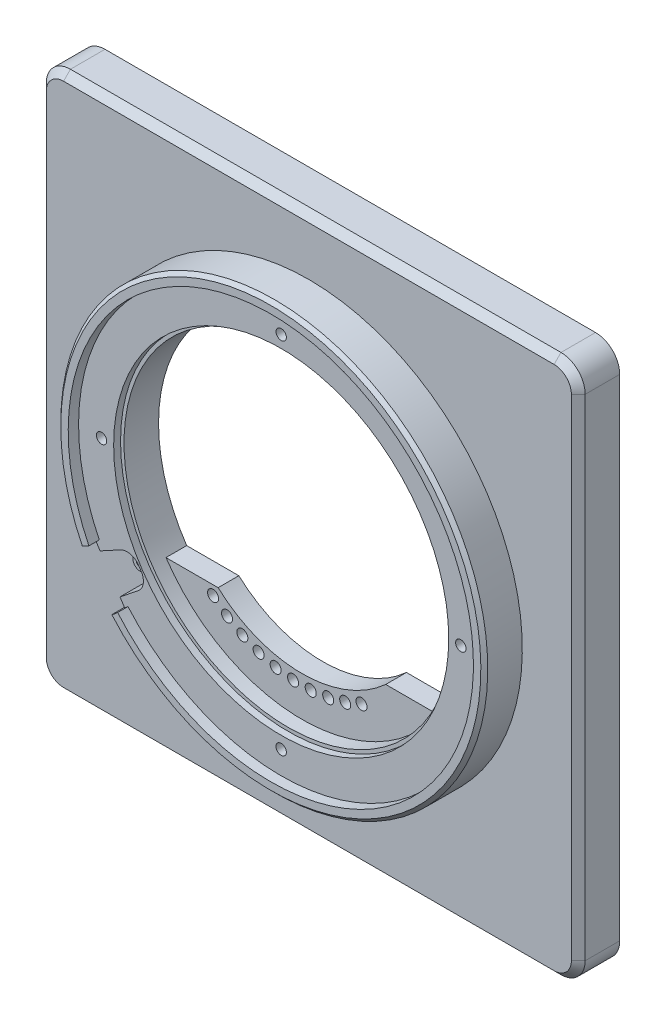
SolidWorks part; units mm, degrees
ref_plane "前视基准面" through (0, 0, 0) normal (0, 0, 1) x (1, 0, 0)
ref_plane "上视基准面" through (0, 0, 0) normal (0, 1, 0) x (1, 0, 0)
ref_plane "右视基准面" through (0, 0, 0) normal (1, 0, 0) x (0, 0, -1)
other "Configuration Table"
sketch "草图1" plane through (0, 0, 0) normal (0, 0, 1) x (1, 0, 0)
  line L1 (-39, -39) -> (39, -39)
  line L2 (-39, -39) -> (-39, 39)
  line L3 (-39, 39) -> (39, 39)
  line L4 (39, -39) -> (39, 39)
  line L5 (-39, -39) -> (39, 39) construction
  line L6 (-39, 39) -> (39, -39) construction
  circle A0 centre (0, 0) radius 23.75
  point P0 (0, 0)
  dimension "D2" = 47.5
  dimension "D1" = 78
extrude "凸台-拉伸1" add sketch "草图1" against normal blind 2
sketch "草图2" plane through (0, 0, 0) normal (0, 0, 1) x (1, 0, 0)
  circle A0 centre (0, 0) radius 23.75
  circle A1 centre (0, 0) radius 23.75 construction
  circle A2 centre (0, 0) radius 30.9
  dimension "D1" = 61.8
extrude "凸台-拉伸2" add sketch "草图2" along normal blind 4
sketch "草图3" plane through (0, 0, -2) normal (0, 0, -1) x (-1, 0, 0)
  line L1 (-39, -39) -> (39, -39)
  line L2 (-39, -39) -> (-39, 39)
  line L3 (-39, 39) -> (39, 39)
  line L4 (39, -39) -> (39, 39)
  line L5 (-39, -39) -> (39, 39) construction
  line L6 (-39, 39) -> (39, -39) construction
  line L7 (-37, -37) -> (37, -37)
  line L8 (-37, -37) -> (-37, 37)
  line L9 (-37, 37) -> (37, 37)
  line L10 (37, -37) -> (37, 37)
  line L11 (-37, -37) -> (37, 37) construction
  line L12 (-37, 37) -> (37, -37) construction
  line L13 (-37, 37) -> (-32, 37)
  line L14 (-37, 37) -> (-37, 32)
  line L15 (-37, 32) -> (-32, 32)
  line L16 (-32, 37) -> (-32, 32)
  line L17 (37, 37) -> (32, 37)
  line L18 (37, 37) -> (37, 32)
  line L19 (37, 32) -> (32, 32)
  line L20 (32, 37) -> (32, 32)
  line L21 (-37, -37) -> (-32, -37)
  line L22 (-37, -37) -> (-37, -32)
  line L23 (-37, -32) -> (-32, -32)
  line L24 (-32, -37) -> (-32, -32)
  line L25 (37, -37) -> (32, -37)
  line L26 (37, -37) -> (37, -32)
  line L27 (37, -32) -> (32, -32)
  line L28 (32, -37) -> (32, -32)
  point P0 (0, 0)
  point P7 (0, 0)
  line M23 (-39, 39) -> (-39, -39)
  line M24 (-39, -39) -> (39, -39)
  line M25 (39, -39) -> (39, 39)
  line M26 (39, 39) -> (-39, 39)
  dimension "D1" = 2
  dimension "D2" = 5
extrude "凸台-拉伸3" add sketch "草图3" along normal blind 4 contours L10 L7 L8 L9 M26 M23 M24 M25 | L16 L9 L8 L15 | L9 L20 L19 L10 | L28 L7 L10 L27 | L7 L24 L23 L8 region at (37.8969, 0, -2) region at (34.5, -34.5, -2) region at (-34.5, -34.5, -2) region at (34.5, 34.5, -2) region at (-34.5, 34.5, -2)
sketch "草图4" plane through (0, 0, 4) normal (0, 0, 1) x (1, 0, 0)
  line L0 (0, 26) -> (0, -26) construction
  line L1 (-26, 0) -> (26, 0) construction
  circle A0 centre (0, 0) radius 26 construction
  circle A1 centre (0, 26) radius 0.75
  circle A2 centre (26, 0) radius 0.75
  circle A3 centre (0, -26) radius 0.75
  circle A4 centre (-26, 0) radius 0.75
  dimension "D2" = 52
  dimension "D3" = 1.5
extrude "切除-拉伸1" cut sketch "草图4" against normal blind 5
sketch "草图5" plane through (0, 0, 4) normal (0, 0, 1) x (1, 0, 0)
  line L0 (-15.4397, 0) -> (13.8511, 0) construction
  line L1 (-27.9748, -13.7193) -> (-23.5593, -20.3904)
  line L2 (-23.5593, -20.3904) -> (0, 0) construction
  line L3 (0, 0) -> (-27.9748, -13.7193) construction
  line L4 (-25.7671, -17.0549) -> (0, 0) construction
  line L5 (-27.9748, -13.7193) -> (-26.8884, -13.1865)
  line L6 (-26.8884, -13.1865) -> (-26.2006, -14.2257)
  line L7 (-26.2006, -14.2257) -> (0, 0) construction
  line L8 (0, 0) -> (-23.3322, -18.5593) construction
  line L9 (-23.3322, -18.5593) -> (-22.6444, -19.5985)
  line L10 (-22.6444, -19.5985) -> (-23.5593, -20.3904)
  line L11 (-26.2006, -14.2257) -> (-23.2413, -12.619)
  line L12 (-20.6192, -13.2728) -> (-20.2742, -13.794)
  line L13 (-20.6969, -16.4631) -> (-23.3322, -18.5593)
  circle A0 centre (0, 0) radius 30.9 construction
  arc A1 (-20.2742, -13.794) -> (-20.6969, -16.4631) centre (-21.942, -14.8979) cw
  arc A2 (-23.2413, -12.619) -> (-20.6192, -13.2728) centre (-22.287, -14.3766) cw
  point P17 (-19.2627, -15.3222)
  point P20 (-21.6307, -11.7445)
  dimension "D6" = 2
  dimension "D1" = 33.5
  dimension "D2" = 8
  dimension "D3" = 5
  dimension "D4" = 1.2
  dimension "D5" = 5.2
extrude "切除-拉伸2" cut sketch "草图5" against normal blind 4
sketch "草图6" plane through (0, 0, 0) normal (0, 0, 1) x (1, 0, 0)
  line L0 (-22.409, -14.8322) -> (0, 0) construction
  line L1 (0, 0) -> (-21.4312, 0) construction
  circle A0 centre (0, 0) radius 26.873 construction
  circle A1 centre (-22.409, -14.8322) radius 0.55
  circle A2 centre (-22.409, -14.8322) radius 1.05
  dimension "D1" = 53.746
  dimension "D3" = 1.1
  dimension "D4" = 2.1
  dimension "D2" = 33.5
extrude "凸台-拉伸4" add sketch "草图6" along normal blind 2
sketch "草图8" plane through (0, 0, 4) normal (0, 0, 1) x (1, 0, 0)
  line L0 (-27.7433, -13.6058) -> (-26.3292, -12.9123)
  line L1 (-23.3644, -20.2217) -> (-22.1735, -19.191)
  circle A0 centre (0, 0) radius 30.9
  circle A1 centre (0, 0) radius 29.325
  arc A2 (-23.3644, -20.2217) -> (-27.7433, -13.6058) centre (0, 0) ccw construction
  line M27 (-27.7433, -13.6058) -> (-26.8884, -13.1865)
  line M35 (-22.6444, -19.5985) -> (-23.3644, -20.2217)
  arc M36 (-23.3644, -20.2217) -> (-27.7433, -13.6058) centre (0, 0) ccw
  dimension "D1" = 58.65
extrude "凸台-拉伸5" add sketch "草图8" along normal blind 1.5 contours A1 L1 L0 M35 M36 M27 region at (-6.7861, 29.2491, 4)
chamfer "倒角1" distance 0.5 angle 45 1 edges at (25.7671, 17.0549, 5.5)
sketch "草图9" plane through (0, 0, -2) normal (0, 0, -1) x (-1, 0, 0)
  line L1 (-19, -19) -> (19, -19) construction
  line L2 (-19, -19) -> (-19, 19) construction
  line L3 (-19, 19) -> (19, 19) construction
  line L4 (19, -19) -> (19, 19) construction
  line L5 (-19, -19) -> (19, 19) construction
  line L6 (-19, 19) -> (19, -19) construction
  circle A0 centre (-19, -19) radius 0.8
  circle A1 centre (-19, -19) radius 1.65
  circle A2 centre (-19, 19) radius 0.8
  circle A3 centre (-19, 19) radius 1.65
  circle A4 centre (19, 19) radius 0.8
  circle A5 centre (19, 19) radius 1.65
  point P0 (0, 0)
  dimension "D2" = 1.6
  dimension "D3" = 3.3
  dimension "D1" = 38
extrude "凸台-拉伸6" add sketch "草图9" along normal blind 2
extrude "切除-拉伸4" cut sketch "草图9<2>" against normal blind 2 contours A2 | A4 | A0 region at (19, -19, -2) region at (19, 19, -2) region at (-19, 19, -2)
sketch "草图9<2>" plane through (0, 0, -2) normal (0, 0, -1) x (-1, 0, 0) same geometry as "草图9"
sketch "草图10" plane through (0, 0, -6) normal (0, 0, -1) x (-1, 0, 0)
  line L0 (39, 39) -> (-39, 39) construction
  line L1 (34.5, -34.5) -> (-34.5, -34.5) construction
  line L2 (34.5, -34.5) -> (34.5, 34.5) construction
  line L3 (34.5, 34.5) -> (-34.5, 34.5) construction
  line L4 (-34.5, -34.5) -> (-34.5, 34.5) construction
  line L5 (34.5, -34.5) -> (-34.5, 34.5) construction
  line L6 (34.5, 34.5) -> (-34.5, -34.5) construction
  circle A0 centre (-34.5, 34.5) radius 0.8
  circle A1 centre (34.5, 34.5) radius 0.8
  circle A2 centre (34.5, -34.5) radius 0.8
  circle A3 centre (-34.5, -34.5) radius 0.8
  point P0 (0, 0)
  dimension "D2" = 1.6
  dimension "D1" = 4.5
extrude "切除-拉伸5" cut sketch "草图10" against normal blind 4
fillet "圆角2" radius 1.5 12 edges at (37, -32, -4) (32, -37, -4) (-32, -37, -4) (-32, -32, -4) (-37, -32, -4) (-37, 32, -4) (-32, 37, -4) (32, -32, -4) (-32, 32, -4) (32, 37, -4) (37, 32, -4) (32, 32, -4)
fillet "圆角3" radius 3.5 4 edges at (39, -39, -3) (-39, -39, -3) (-39, 39, -3) (39, 39, -3)
chamfer "倒角2" distance 1 angle 45 8 edges at (0, -39, 0) (37.9749, -37.9749, 0) (-37.9749, -37.9749, 0) (39, 0, 0) (-39, 0, 0) (37.9749, 37.9749, 0) (-37.9749, 37.9749, 0) (0, 39, 0)
sketch "草图11" plane through (0, 0, 4) normal (0, 0, 1) x (1, 0, 0)
  circle A0 centre (0, 0) radius 24.25
  dimension "D1" = 48.5
extrude "切除-拉伸6" cut sketch "草图11" against normal blind 1
sketch "草图12" plane through (0, 0, -6) normal (0, 0, -1) x (-1, 0, 0)
  line L0 (-30.5, 37) -> (30.5, 37) construction
  line L1 (-25, 37) -> (25, 37)
  line L2 (-25, 37) -> (-25, 38)
  line L3 (-25, 38) -> (25, 38)
  line L4 (25, 37) -> (25, 38)
  line L5 (37, -30.5) -> (37, 30.5) construction
  line L6 (37, 25) -> (38, 25)
  line L7 (37, 25) -> (37, -25)
  line L8 (37, -25) -> (38, -25)
  line L9 (38, 25) -> (38, -25)
  line L10 (-30.5, -37) -> (30.5, -37) construction
  line L11 (25, -37) -> (-25, -37)
  line L12 (25, -37) -> (25, -38)
  line L13 (25, -38) -> (-25, -38)
  line L14 (-25, -37) -> (-25, -38)
  line L15 (-37, -30.5) -> (-37, 30.5) construction
  line L16 (-37, -25) -> (-38, -25)
  line L17 (-37, -25) -> (-37, 25)
  line L18 (-37, 25) -> (-38, 25)
  line L19 (-38, -25) -> (-38, 25)
  line L20 (0, -4.6052) -> (0, 11.8131) construction
  line L21 (-9.8593, 0) -> (12.3811, 0) construction
  dimension "D1" = 50
  dimension "D2" = 1
extrude "切除-拉伸7" cut sketch "草图12" against normal blind 1
sketch "草图14" plane through (0, 0, -2) normal (0, 0, -1) x (-1, 0, 0)
  line L0 (-19.6767, -13.3) -> (19.6767, -13.3)
  line L1 (50.4413, 154.8247) -> (517.1079, 154.8247) construction
  line L2 (0, 0) -> (0, -19.5) construction
  line L3 (0, 0) -> (12.8572, -14.6609) construction
  line L4 (0, 0) -> (10.8336, -16.2137) construction
  line L12 (12.8572, -14.6609) -> (0, 0)
  circle A0 centre (0, 0) radius 23.75 construction
  circle A10 centre (12.8572, -14.6609) radius 0.8
  circle A11 centre (0, 0) radius 19.5 construction
  circle A12 centre (10.8336, -16.2137) radius 0.8
  circle A13 centre (8.6246, -17.489) radius 0.8
  circle A14 centre (6.2681, -18.4651) radius 0.8
  circle A15 centre (3.8043, -19.1253) radius 0.8
  circle A16 centre (1.2754, -19.4582) radius 0.8
  circle A17 centre (-1.2754, -19.4582) radius 0.8
  circle A18 centre (-3.8043, -19.1253) radius 0.8
  circle A19 centre (-6.2681, -18.4651) radius 0.8
  circle A20 centre (-8.6246, -17.489) radius 0.8
  arc A21 (12.1289, -13.3) -> (-12.1289, -13.3) centre (0, 0) cw
  circle M44 centre (0, 0) radius 23.75
  dimension "D2" = 39
  dimension "D3" = 1.6
  dimension "D7" = 18
  dimension "D1" = 13.3
  dimension "D4" = 41.25
  dimension "D6" = 7.5
  dimension "D5" = 10
extrude "凸台-拉伸7" add sketch "草图14" against normal blind 3 contours L0 A21 A10 A20 A19 A18 A17 A16 A15 A14 A13 A12 M44 region at (0.2498, -18.4971, -2)
